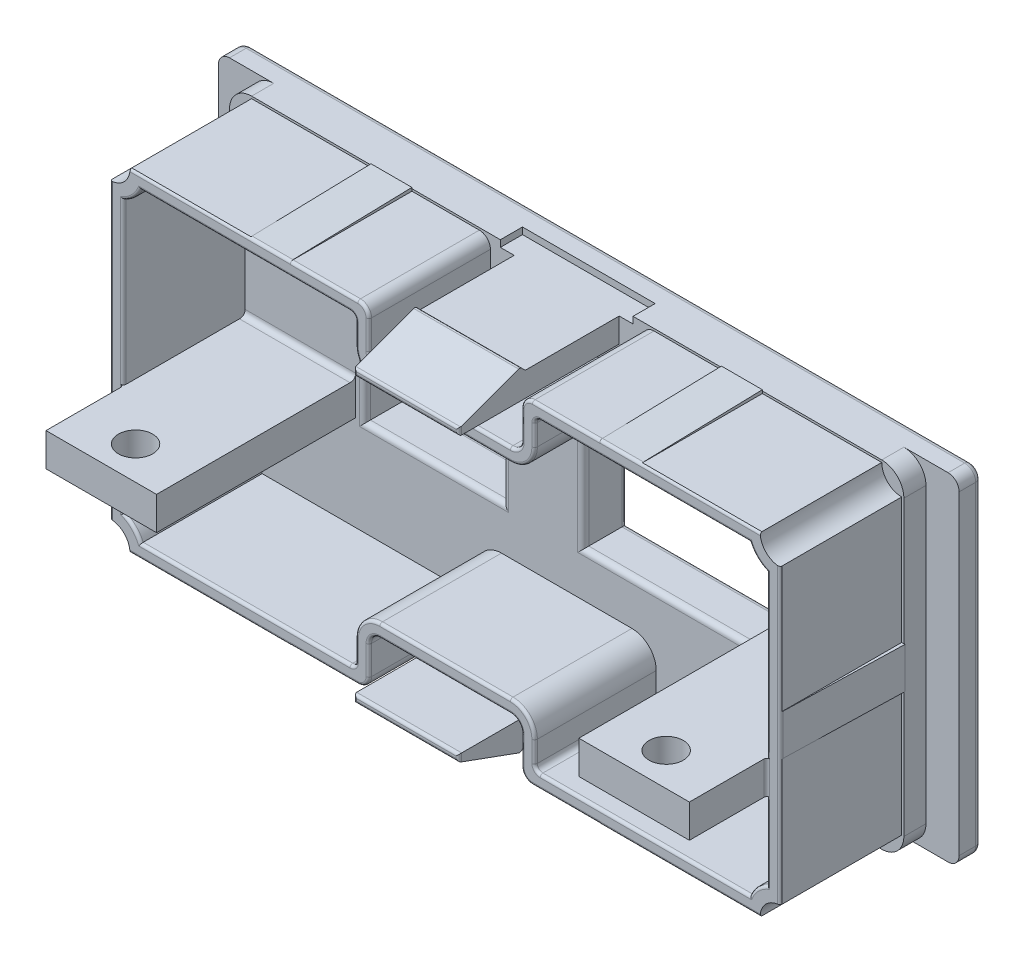
SolidWorks part; units mm, degrees
ref_plane "Front Plane" through (0, 0, 0) normal (0, 0, 1) x (1, 0, 0)
ref_plane "Top Plane" through (0, 0, 0) normal (0, 1, 0) x (1, 0, 0)
ref_plane "Right Plane" through (0, 0, 0) normal (1, 0, 0) x (0, 0, -1)
sketch "Sketch1" plane through (0, 0, 0) normal (0, 0, 1) x (1, 0, 0)
  line L1 (-32.5, 15.25) -> (32.5, 15.25)
  line L2 (-33.5, 14.25) -> (-33.5, -14.25)
  line L3 (-32.5, -15.25) -> (32.5, -15.25)
  line L4 (33.5, 14.25) -> (33.5, -14.25)
  line L5 (-33.5, 15.25) -> (33.5, -15.25) construction
  line L6 (-33.5, -15.25) -> (33.5, 15.25) construction
  arc A0 (-33.5, -14.25) -> (-32.5, -15.25) centre (-32.5, -14.25) ccw
  arc A1 (32.5, -15.25) -> (33.5, -14.25) centre (32.5, -14.25) ccw
  arc A2 (32.5, 15.25) -> (33.5, 14.25) centre (32.5, 14.25) cw
  arc A3 (-32.5, 15.25) -> (-33.5, 14.25) centre (-32.5, 14.25) ccw
  dimension "D1" = 1
  dimension "D2" = 30.5
  dimension "D3" = 67
extrude "Boss-Extrude1" add sketch "Sketch1" along normal blind 2
fillet "Fillet2" radius 0.5 8 edges at (0, -15.25, 0) (33.2071, -14.9571, 0) (33.5, 0, 0) (33.2071, 14.9571, 0) (0, 15.25, 0) (-33.2071, 14.9571, 0) (-33.5, 0, 0) (-33.2071, -14.9571, 0)
sketch "Sketch2" plane through (0, 0, 2) normal (0, 0, 1) x (1, 0, 0)
  line L1 (-28.5, 15.25) -> (28.5, 15.25)
  line L2 (-30.5, 13.25) -> (-30.5, -13.25)
  line L3 (-28.5, -15.25) -> (28.5, -15.25)
  line L4 (30.5, 13.25) -> (30.5, -13.25)
  line L5 (-30.5, 15.25) -> (30.5, -15.25) construction
  line L6 (-30.5, -15.25) -> (30.5, 15.25) construction
  line L7 (32.5, 15.25) -> (-32.5, 15.25) construction
  line L8 (33.5, -14.25) -> (33.5, 14.25) construction
  arc A0 (-30.5, -13.25) -> (-28.5, -15.25) centre (-28.5, -13.25) ccw
  arc A1 (28.5, -15.25) -> (30.5, -13.25) centre (28.5, -13.25) ccw
  arc A2 (28.5, 15.25) -> (30.5, 13.25) centre (28.5, 13.25) cw
  arc A3 (-28.5, 15.25) -> (-30.5, 13.25) centre (-28.5, 13.25) ccw
  point P0 (0, 0)
  dimension "D2" = 2
  dimension "D1" = 3
extrude "Boss-Extrude2" add sketch "Sketch2" along normal blind 2
sketch "Sketch4" plane through (0, 0, 0) normal (0, 0, -1) x (-1, 0, 0)
  line L0 (32.5, -15.25) -> (-32.5, -15.25) construction
  line L1 (-18.5, 8.75) -> (-1.5, 8.75)
  line L2 (-18.5, 8.75) -> (-18.5, -5.25)
  line L3 (-18.5, -5.25) -> (-1.5, -5.25)
  line L4 (-1.5, 8.75) -> (-1.5, -5.25)
  line L5 (-18.5, 8.75) -> (-1.5, -5.25) construction
  line L6 (-18.5, -5.25) -> (-1.5, 8.75) construction
  line L7 (5.75, 5.75) -> (18.25, 5.75)
  line L8 (5.75, 5.75) -> (5.75, -5.25)
  line L9 (5.75, -5.25) -> (18.25, -5.25)
  line L10 (18.25, 5.75) -> (18.25, -5.25)
  line L11 (5.75, 5.75) -> (18.25, -5.25) construction
  line L12 (5.75, -5.25) -> (18.25, 5.75) construction
  point P0 (-10, 1.75)
  point P5 (12, 0.25)
  dimension "D1" = 10
  dimension "D2" = 14
  dimension "D3" = 17
  dimension "D4" = 12.5
  dimension "D5" = 11
  dimension "D6" = 10
  dimension "D7" = 12
extrude "Cut-Extrude1" cut sketch "Sketch4" against normal through all
fillet "Fillet3" radius 0.5 8 edges at (-12, -5.25, 0) (-18.25, 0.25, 0) (-12, 5.75, 0) (-5.75, 0.25, 0) (1.5, 1.75, 0) (10, 8.75, 0) (18.5, 1.75, 0) (10, -5.25, 0)
sketch "Sketch5" plane through (0, 0, 4) normal (0, 0, 1) x (1, 0, 0)
  line L1 (28.5, 15.25) -> (-28.5, 15.25) construction
  line L3 (-28.5, -15.25) -> (28.5, -15.25) construction
  line L8 (-6.9, 14.05) -> (-6.9, 11.45)
  line L9 (-5.9, 10.45) -> (5.9, 10.45)
  line L10 (6.9, 11.45) -> (6.9, 14.05)
  line L11 (-28.5, 15.05) -> (-7.9, 15.05)
  line L12 (7.9, 15.05) -> (28.5, 15.05)
  line L13 (27.5505, -13.85) -> (8.1, -13.85)
  line L14 (-6.9, -14.05) -> (-6.9, -11.45)
  line L15 (-5.9, -10.45) -> (5.9, -10.45)
  line L16 (-30.3, 13.25) -> (-30.3, -13.25)
  line L17 (-30.5, 13.25) -> (-30.5, -13.25) construction
  line L18 (6.9, -11.45) -> (6.9, -14.05)
  line L19 (-30.5, 13.25) -> (-30.5, -13.25) construction
  line L20 (-7.9, -15.05) -> (-28.5, -15.05)
  line L21 (30.3, 13.25) -> (30.3, -13.25)
  line L22 (8.1, -11.45) -> (8.1, -13.85)
  line L23 (-5.9, -9.25) -> (5.9, -9.25)
  line L24 (-8.1, -13.85) -> (-8.1, -11.45)
  line L25 (-8.1, -13.85) -> (-27.5505, -13.85)
  line L26 (-29.1, 12.3005) -> (-29.1, -12.3005)
  line L27 (-27.5505, 13.85) -> (-8.1, 13.85)
  line L28 (28.5, -15.05) -> (7.9, -15.05)
  line L29 (-8.1, 13.85) -> (-8.1, 11.45)
  line L30 (-5.9, 9.25) -> (5.9, 9.25)
  line L31 (8.1, 11.45) -> (8.1, 13.85)
  line L32 (8.1, 13.85) -> (27.5505, 13.85)
  line L33 (29.1, 12.3005) -> (29.1, -12.3005)
  arc A1 (30.3, -13.25) -> (28.5, -15.05) centre (30.3, -15.05) ccw
  arc A2 (28.5, 15.05) -> (30.3, 13.25) centre (30.3, 15.05) ccw
  arc A3 (-28.5, 15.05) -> (-30.3, 13.25) centre (-30.3, 15.05) cw
  arc A4 (-28.5, -15.05) -> (-30.3, -13.25) centre (-30.3, -15.05) ccw
  arc A5 (6.9, -14.05) -> (7.9, -15.05) centre (7.9, -14.05) ccw
  arc A6 (5.9, -10.45) -> (6.9, -11.45) centre (5.9, -11.45) cw
  arc A7 (-6.9, -14.05) -> (-7.9, -15.05) centre (-7.9, -14.05) cw
  arc A8 (-6.9, -11.45) -> (-5.9, -10.45) centre (-5.9, -11.45) cw
  arc A9 (6.9, 14.05) -> (7.9, 15.05) centre (7.9, 14.05) cw
  arc A10 (5.9, 10.45) -> (6.9, 11.45) centre (5.9, 11.45) ccw
  arc A11 (-6.9, 11.45) -> (-5.9, 10.45) centre (-5.9, 11.45) ccw
  arc A12 (-6.9, 14.05) -> (-7.9, 15.05) centre (-7.9, 14.05) ccw
  arc A13 (8.1, -13.85) -> (8.1, -13.85) centre (8.1, -13.85) ccw
  arc A14 (5.9, -9.25) -> (8.1, -11.45) centre (5.9, -11.45) cw
  arc A15 (-8.1, -11.45) -> (-5.9, -9.25) centre (-5.9, -11.45) cw
  arc A16 (-8.1, -13.85) -> (-8.1, -13.85) centre (-8.1, -13.85) cw
  arc A17 (-27.5505, -13.85) -> (-29.1, -12.3005) centre (-30.3, -15.05) ccw
  arc A18 (-27.5505, 13.85) -> (-29.1, 12.3005) centre (-30.3, 15.05) cw
  arc A19 (-8.1, 13.85) -> (-8.1, 13.85) centre (-8.1, 13.85) ccw
  arc A20 (-8.1, 11.45) -> (-5.9, 9.25) centre (-5.9, 11.45) ccw
  arc A21 (5.9, 9.25) -> (8.1, 11.45) centre (5.9, 11.45) ccw
  arc A22 (8.1, 13.85) -> (8.1, 13.85) centre (8.1, 13.85) cw
  arc A23 (27.5505, 13.85) -> (29.1, 12.3005) centre (30.3, 15.05) ccw
  arc A24 (29.1, -12.3005) -> (27.5505, -13.85) centre (30.3, -15.05) ccw
  point P6 (0, 10.45)
  dimension "D4" = 1
  dimension "D1" = 0.2
  dimension "D2" = 0.2
  dimension "D3" = 4.6
  dimension "D6" = 13.8
  dimension "D5" = 0.2
  dimension "D7" = 0.2
  dimension "D8" = 1.2
extrude "Boss-Extrude3" add sketch "Sketch5" along normal blind 11
fillet "Fillet5" radius 0.5 4 edges at (-8.1, -13.85, 9.5) (8.1, -13.85, 9.5) (8.1, 13.85, 9.5) (-8.1, 13.85, 9.5)
sketch "Sketch6" plane through (0, 0, 4) normal (0, 0, 1) x (1, 0, 0)
  line L1 (-6, 15.25) -> (6, 15.25)
  line L2 (-6, 15.25) -> (-6, 14.65)
  line L3 (-6, 14.65) -> (6, 14.65)
  line L4 (6, 15.25) -> (6, 14.65)
  line L5 (-6, 15.25) -> (6, 14.65) construction
  line L6 (-6, 14.65) -> (6, 15.25) construction
  line L7 (-6, -14.65) -> (6, -14.65)
  line L8 (-6, -14.65) -> (-6, -15.25)
  line L9 (-6, -15.25) -> (6, -15.25)
  line L10 (6, -14.65) -> (6, -15.25)
  line L11 (-6, -14.65) -> (6, -15.25) construction
  line L12 (-6, -15.25) -> (6, -14.65) construction
  line L13 (28.5, 15.25) -> (-28.5, 15.25) construction
  line L14 (-28.5, -15.25) -> (28.5, -15.25) construction
  point P0 (0, 14.95)
  point P5 (0, -14.95)
  dimension "D1" = 12
  dimension "D2" = 0.6
extrude "Cut-Extrude2" cut sketch "Sketch6" against normal blind 2
sketch "Sketch7" plane through (0, 0, 4) normal (0, 0, 1) x (1, 0, 0)
  line L0 (-6, 14.65) -> (6, 14.65) construction
  line L1 (-4.75, 14.65) -> (4.75, 14.65)
  line L2 (-4.75, 14.65) -> (-4.75, 12.45)
  line L3 (-4.75, 12.45) -> (4.75, 12.45)
  line L4 (4.75, 14.65) -> (4.75, 12.45)
  line L5 (-4.75, 14.65) -> (4.75, 12.45) construction
  line L6 (-4.75, 12.45) -> (4.75, 14.65) construction
  line L7 (-4.75, -12.45) -> (4.75, -12.45)
  line L8 (-4.75, -12.45) -> (-4.75, -14.65)
  line L9 (-4.75, -14.65) -> (4.75, -14.65)
  line L10 (4.75, -12.45) -> (4.75, -14.65)
  line L11 (-4.75, -12.45) -> (4.75, -14.65) construction
  line L12 (-4.75, -14.65) -> (4.75, -12.45) construction
  line L13 (6, -14.65) -> (-6, -14.65) construction
  point P0 (0, 13.55)
  point P5 (0, -13.55)
  dimension "D1" = 2.2
  dimension "D2" = 9.5
extrude "Boss-Extrude4" add sketch "Sketch7" along normal blind 8.5
sketch "Sketch10" plane through (0, 0, 12.5) normal (0, 0, 1) x (1, 0, 0)
  line L1 (-4.75, 15.25) -> (4.75, 15.25)
  line L2 (-4.75, 15.25) -> (-4.75, 12.45)
  line L3 (-4.75, 12.45) -> (4.75, 12.45)
  line L4 (4.75, 15.25) -> (4.75, 12.45)
  line L5 (-4.75, 15.25) -> (4.75, 12.45) construction
  line L6 (-4.75, 12.45) -> (4.75, 15.25) construction
  line L8 (-4.75, 12.45) -> (4.75, 12.45) construction
  line L9 (4.75, 12.45) -> (4.75, 14.65) construction
  line L10 (-4.75, 14.65) -> (-4.75, 12.45) construction
  line L11 (6, 15.25) -> (-6, 15.25) construction
  point P0 (0, 13.85)
extrude "Boss-Extrude5" add sketch "Sketch10" along normal blind 6
sketch "Sketch11" plane through (0, 0, 12.5) normal (0, 0, 1) x (1, 0, 0)
  line L0 (4.75, -14.65) -> (4.75, -12.45) construction
  line L1 (-4.75, -12.45) -> (4.75, -12.45)
  line L2 (-4.75, -12.45) -> (-4.75, -15.25)
  line L3 (-4.75, -15.25) -> (4.75, -15.25)
  line L4 (4.75, -12.45) -> (4.75, -15.25)
  line L5 (-4.75, -12.45) -> (4.75, -15.25) construction
  line L6 (-4.75, -15.25) -> (4.75, -12.45) construction
  line L7 (-4.75, -12.45) -> (-4.75, -14.65) construction
  line L8 (4.75, -12.45) -> (-4.75, -12.45) construction
  line L10 (-6, -15.25) -> (6, -15.25) construction
  point P0 (0, -13.85)
extrude "Boss-Extrude6" add sketch "Sketch11" along normal blind 6
draft "Draft3" type of draft neutral plane draft angle 20 faces to draft 1 face at (0, 15.25, 15.5) neutral plane through (0, 0, 12.5) neutral plane normal (0, 0, -1) reverse direction yes parameters "D1"=20
draft "Draft4" type of draft neutral plane draft angle 45 faces to draft 1 face at (0, 14.95, 12.5) neutral plane through (-6, 14.65, 2) neutral plane normal (0, 1, 0) parameters "D1"=45
draft "Draft5" type of draft neutral plane draft angle 20 faces to draft 1 face at (0, -15.25, 15.5) neutral plane through (0, 0, 12.5) neutral plane normal (0, 0, -1) reverse direction yes parameters "D1"=20
draft "Draft6" type of draft neutral plane draft angle 45 faces to draft 1 face at (0, -14.95, 12.5) neutral plane through (-6, -14.65, 2) neutral plane normal (0, -1, 0) parameters "D1"=45
fillet "Fillet11" radius 0.25 10 edges at (0, -13.0662, 18.5) (-4.75, -12.7581, 18.5) (0, -12.45, 18.5) (4.75, -12.7581, 18.5) (0, 12.45, 18.5) (-4.75, 12.7581, 18.5) (0, 13.0662, 18.5) (4.75, 12.7581, 18.5) (0, -15.0899, 12.9399) (0, 15.0899, 12.9399)
sketch "Sketch12" plane through (0, 15.05, 0) normal (0, 1, 0) x (1, 0, 0)
  line L0 (-7.9, -4) -> (-28.5, -4) construction
  line L1 (14, -4) -> (17.7, -4)
  line L2 (14, -4) -> (14, -15)
  line L3 (14, -15) -> (17.7, -15)
  line L4 (17.7, -4) -> (17.7, -15)
  line L5 (14, -4) -> (17.7, -15) construction
  line L6 (14, -15) -> (17.7, -4) construction
  line L7 (-17.7, -4) -> (-14, -4)
  line L8 (-17.7, -4) -> (-17.7, -15)
  line L9 (-17.7, -15) -> (-14, -15)
  line L10 (-14, -4) -> (-14, -15)
  line L11 (-17.7, -4) -> (-14, -15) construction
  line L12 (-17.7, -15) -> (-14, -4) construction
  line L13 (-7.9, -15) -> (-28.5, -15) construction
  point P0 (15.85, -9.5)
  point P5 (-15.85, -9.5)
  dimension "D1" = 3.7
  dimension "D2" = 14
  dimension "D3" = 14
extrude "Boss-Extrude7" add sketch "Sketch12" along normal blind 0.3
sketch "Sketch14" plane through (0, -15.05, 0) normal (0, -1, 0) x (1, 0, 0)
  line L0 (14, 15) -> (17.7, 15)
  line L1 (14, 15) -> (14, 4)
  line L2 (14, 4) -> (17.7, 4)
  line L3 (17.7, 15) -> (17.7, 4)
  line L4 (14, 15) -> (17.7, 4) construction
  line L5 (14, 4) -> (17.7, 15) construction
  line L6 (-17.7, 15) -> (-14, 15)
  line L7 (-17.7, 15) -> (-17.7, 4)
  line L8 (-17.7, 4) -> (-14, 4)
  line L9 (-14, 15) -> (-14, 4)
  line L10 (-17.7, 15) -> (-14, 4) construction
  line L11 (-17.7, 4) -> (-14, 15) construction
  line L12 (-28.5, 4) -> (-7.9, 4) construction
  line L19 (7.9, 4) -> (28.5, 4) construction
  point P0 (15.85, 9.5)
  point P5 (-15.85, 9.5)
  dimension "D1" = 3.7
  dimension "D2" = 14
  dimension "D3" = 14
extrude "Boss-Extrude10" add sketch "Sketch14" along normal blind 0.3
sketch "Sketch15" plane through (-30.3, 0, 0) normal (-1, 0, 0) x (0, 0, 1)
  line L0 (4, 13.25) -> (4, -13.25) construction
  line L1 (4, 1.85) -> (15, 1.85)
  line L2 (4, 1.85) -> (4, -1.85)
  line L3 (4, -1.85) -> (15, -1.85)
  line L4 (15, 1.85) -> (15, -1.85)
  line L5 (4, 1.85) -> (15, -1.85) construction
  line L6 (4, -1.85) -> (15, 1.85) construction
  line L7 (15, 13.25) -> (15, -13.25) construction
  point P0 (9.5, 0)
  dimension "D1" = 3.7
extrude "Boss-Extrude11" add sketch "Sketch15" along normal blind 0.3
sketch "Sketch16" plane through (30.3, 0, 0) normal (1, 0, 0) x (0, 0, -1)
  line L0 (-4, -13.25) -> (-4, 13.25) construction
  line L1 (-15, 1.85) -> (-4, 1.85)
  line L2 (-15, 1.85) -> (-15, -1.85)
  line L3 (-15, -1.85) -> (-4, -1.85)
  line L4 (-4, 1.85) -> (-4, -1.85)
  line L5 (-15, 1.85) -> (-4, -1.85) construction
  line L6 (-15, -1.85) -> (-4, 1.85) construction
  line L7 (-15, -13.25) -> (-15, 13.25) construction
  point P0 (-9.5, 0)
  dimension "D1" = 3.7
extrude "Boss-Extrude12" add sketch "Sketch16" along normal blind 0.3
sketch "Sketch17" plane through (0, 0, 4) normal (0, 0, 1) x (1, 0, 0)
  line L0 (-29.1, 12.3005) -> (-29.1, -12.3005) construction
  line L1 (-29.1, -2.25) -> (-19.1, -2.25)
  line L2 (-29.1, -2.25) -> (-29.1, -5.25)
  line L3 (-29.1, -5.25) -> (-19.1, -5.25)
  line L4 (-19.1, -2.25) -> (-19.1, -5.25)
  line L5 (-29.1, -2.25) -> (-19.1, -5.25) construction
  line L6 (-29.1, -5.25) -> (-19.1, -2.25) construction
  line L7 (19.1, -2.25) -> (29.1, -2.25)
  line L8 (19.1, -2.25) -> (19.1, -5.25)
  line L9 (19.1, -5.25) -> (29.1, -5.25)
  line L10 (29.1, -2.25) -> (29.1, -5.25)
  line L11 (19.1, -2.25) -> (29.1, -5.25) construction
  line L12 (19.1, -5.25) -> (29.1, -2.25) construction
  line L13 (29.1, -12.3005) -> (29.1, 12.3005) construction
  line L17 (-5.75, -5.25) -> (-18.25, -5.25) construction
  point P0 (-24.1, -3.75)
  point P5 (24.1, -3.75)
  dimension "D1" = 3
  dimension "D2" = 10
extrude "Boss-Extrude13" add sketch "Sketch17" along normal blind 18
sketch "Sketch19" plane through (0, -2.25, 0) normal (0, 1, 0) x (1, 0, 0)
  line L0 (-17.7, -4) -> (-28.5, -4) construction
  circle A0 centre (-24, -19) radius 1.55
  circle A1 centre (24, -19) radius 1.55
  dimension "D1" = 3.1
  dimension "D2" = 24
  dimension "D3" = 24
  dimension "D4" = 15
extrude "Cut-Extrude4" cut sketch "Sketch19" against normal through all
draft "Draft12" type of draft neutral plane draft angle 1.5 faces to draft 6 face at (-15.85, -15.35, 9.5) face at (15.85, -15.35, 9.5) face at (30.6, 0, 9.5) face at (-30.6, 0, 9.5) face at (15.85, 15.35, 9.5) face at (-15.85, 15.35, 9.5) neutral plane through (-28.5, -13.25, 4) neutral plane normal (0, 0, 1) parameters "D1"=1.5
fillet "Fillet20" radius 0.25 1 edges at (29.1, -3.75, 15)
fillet "Fillet21" radius 0.25 1 edges at (-29.1, -3.75, 15)
fillet "Fillet22" radius 0.25 13 edges at (-8.2464, -13.7036, 15) (8.2464, -13.7036, 15) (29.1, -8.7752, 15) (-29.1, -8.7752, 15) (-28.1787, -12.9287, 15) (-18.0752, -13.85, 15) (-8.1, -12.4, 15) (-7.4556, -9.8944, 15) (0, -9.25, 15) (7.4556, -9.8944, 15) (8.1, -12.4, 15) (18.0752, -13.85, 15) (28.1787, -12.9287, 15)
fillet "Fillet23" radius 0.25 13 edges at (8.2464, 13.7036, 15) (-8.2464, 13.7036, 15) (29.1, 5.0252, 15) (28.1787, 12.9287, 15) (18.0752, 13.85, 15) (8.1, 12.4, 15) (7.4556, 9.8944, 15) (0, 9.25, 15) (-7.4556, 9.8944, 15) (-8.1, 12.4, 15) (-18.0752, 13.85, 15) (-28.1787, 12.9287, 15) (-29.1, 5.0252, 15)
fillet "Fillet25" radius 0.25 1 edges at (15.85, -15.062, 15)
fillet "Fillet26" radius 0.25 1 edges at (-30.312, 0, 15)
fillet "Fillet27" radius 0.25 1 edges at (30.312, 0, 15)
fillet "Fillet28" radius 0.25 1 edges at (15.85, 15.062, 15)
fillet "Fillet29" radius 0.25 1 edges at (-15.85, -15.062, 15)
fillet "Fillet30" radius 0.25 9 edges at (10.95, -15.05, 14.8442) (6.9945, -14.4743, 15) (6.9, -12.75, 15) (6.6071, -10.7429, 15) (0, -10.45, 15) (-6.6071, -10.7429, 15) (-6.9, -12.75, 15) (-6.9945, -14.4743, 15) (-10.95, -15.05, 14.8442)
fillet "Fillet31" radius 0.25 9 edges at (10.95, 15.05, 14.8442) (6.9945, 14.4743, 15) (6.9, 12.75, 15) (6.6071, 10.7429, 15) (0, 10.45, 15) (-6.6071, 10.7429, 15) (-6.9, 12.75, 15) (-7.1929, 14.7571, 15) (-10.95, 15.05, 15)
fillet "Fillet32" radius 0.25 1 edges at (-15.85, 15.062, 15)
fillet "Fillet36" radius 0.5 8 edges at (10, -5.25, 4) (18.5, 1.75, 4) (10, 8.75, 4) (1.5, 1.75, 4) (-18.25, 0.25, 4) (-12, -5.25, 4) (-5.75, 0.25, 4) (-12, 5.75, 4) conic rho 0.5
fillet "Fillet37" radius 0.5 2 edges at (24.1, -2.25, 4) (-24.1, -2.25, 4) conic rho 0.5
